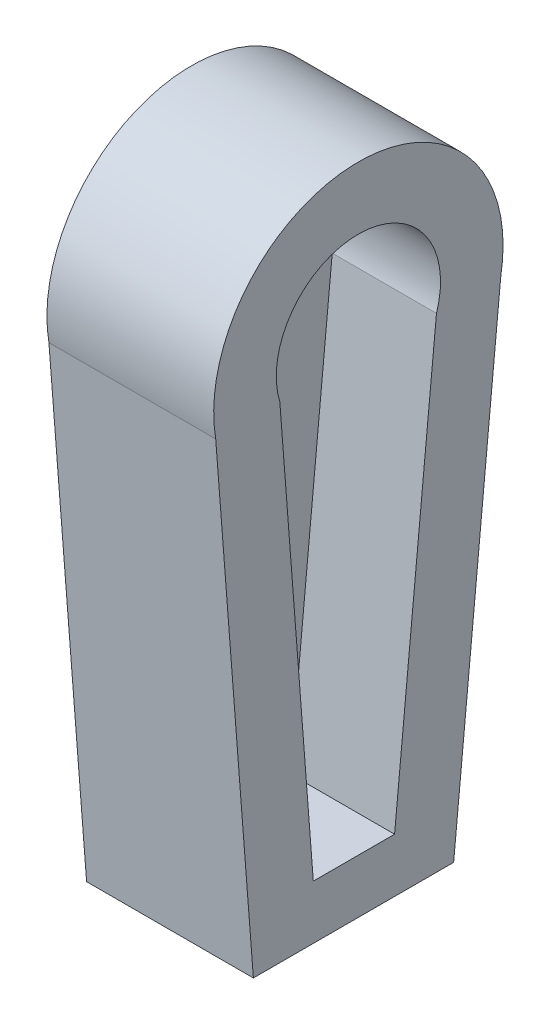
SolidWorks part; units mm, degrees
ref_plane "Front Plane" through (0, 0, 0) normal (0, 0, 1) x (1, 0, 0)
ref_plane "Top Plane" through (0, 0, 0) normal (0, 1, 0) x (1, 0, 0)
ref_plane "Right Plane" through (0, 0, 0) normal (1, 0, 0) x (0, 0, -1)
sketch "Sketch1" plane through (0, 0, 0) normal (1, 0, 0) x (0, 0, -1)
  line L0 (114.5565, 367.603) -> (601.2232, 367.603) construction
  line L1 (-274.0854, -38.501) -> (212.5813, -38.501) construction
  line L2 (-3.7689, -1.1477) -> (-2.162, -21.8566)
  line L3 (3.7456, -1.2216) -> (1.7358, -21.8566)
  line L4 (1.7358, -21.8566) -> (-2.162, -21.8566)
  line L5 (3.7456, -1.2216) -> (-3.7689, -1.1477) construction
  line L6 (-3.7689, -1.1477) -> (-13.6167, -1.1477) construction
  line L7 (3.7456, -1.2216) -> (11.3163, -1.2216) construction
  line L8 (-6.8442, -1.1477) -> (-5.0367, -24.4431)
  line L9 (-5.0367, -24.4431) -> (4.5696, -24.4431)
  line L10 (4.5696, -24.4431) -> (6.8314, -1.2216)
  circle A0 centre (0, 0) radius 2.375
  arc A1 (-3.7689, -1.1477) -> (3.7456, -1.2216) centre (0, 0) cw
  arc A2 (-6.8442, -1.1477) -> (6.8314, -1.2216) centre (0, 0) cw
  point P15 (3.7456, -21.7067)
  point P18 (0, 0)
  point P19 (-1.0068, -21.9626)
  point P20 (2.9042, -21.9372)
  dimension "D1" = 4.75
  dimension "D2" = 3
  dimension "D3" = 85
  dimension "D4" = 85
extrude "Boss-Extrude1" add sketch "Sketch1" along normal blind 8 contours A2 L8 L9 L10 L2 A1 L3 L4 region at (0, 6.5965, -0.0356)
extrude "Boss-Extrude2" add sketch "Sketch1<3>" along normal blind 3 contours A1 L2 L4 L3 A0 region at (0, -8.9288, 0.0881)
sketch "Sketch1<3>" plane through (0, 0, 0) normal (1, 0, 0) x (0, 0, -1) same geometry as "Sketch1"
